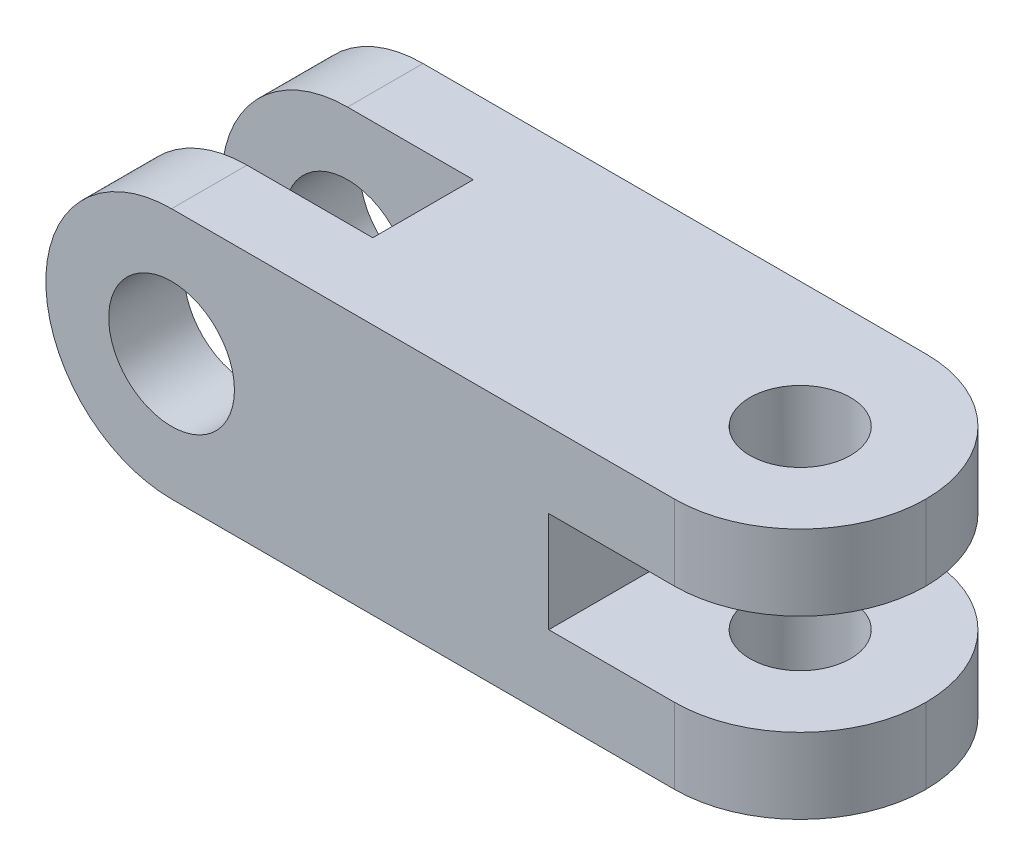
SolidWorks part; units mm, degrees
ref_plane "Front Plane" through (0, 0, 0) normal (0, 0, 1) x (1, 0, 0)
ref_plane "Top Plane" through (0, 0, 0) normal (0, 1, 0) x (1, 0, 0)
ref_plane "Right Plane" through (0, 0, 0) normal (1, 0, 0) x (0, 0, -1)
sketch "Sketch1" plane through (0, 0, 0) normal (0, 0, 1) x (1, 0, 0)
  line L1 (0, 0) -> (125, 0)
  line L3 (0, 50) -> (125, 50)
  line L4 (125, 0) -> (125, 50)
  line L5 (125, 35) -> (75, 35)
  line L6 (125, 35) -> (125, 15)
  line L7 (125, 15) -> (75, 15)
  line L8 (75, 35) -> (75, 15)
  circle A0 centre (0, 25) radius 12.5
  arc A1 (0, 50) -> (0, 0) centre (0, 25) ccw
  dimension "D3" = 50
  dimension "D4" = 25
  dimension "D1" = 125
  dimension "D2" = 50
  dimension "D5" = 50
  dimension "D6" = 15
  dimension "D7" = 15
extrude "Boss-Extrude1" add sketch "Sketch1" along normal blind 50 contours L3 A1 L1 L4 L7 L8 L5 A0 region at (48.8094, 25, 0)
fillet "Fillet1" radius 25 4 edges at (125, 7.5, 0) (125, 42.5, 0) (125, 7.5, 50) (125, 42.5, 50)
sketch "Sketch2" plane through (0, 50, 0) normal (0, 1, 0) x (1, 0, 0)
  line L1 (-25, 0) -> (-25, -50) construction
  line L2 (-25, -15) -> (25, -15)
  line L3 (-25, -15) -> (-25, -35)
  line L4 (-25, -35) -> (25, -35)
  line L5 (25, -15) -> (25, -35)
  line L6 (0, 0) -> (100, 0) construction
  circle A0 centre (100, -25) radius 10
  dimension "D1" = 20
  dimension "D2" = 50
  dimension "D3" = 20
  dimension "D4" = 15
extrude "Cut-Extrude1" cut sketch "Sketch2" against normal blind 55
